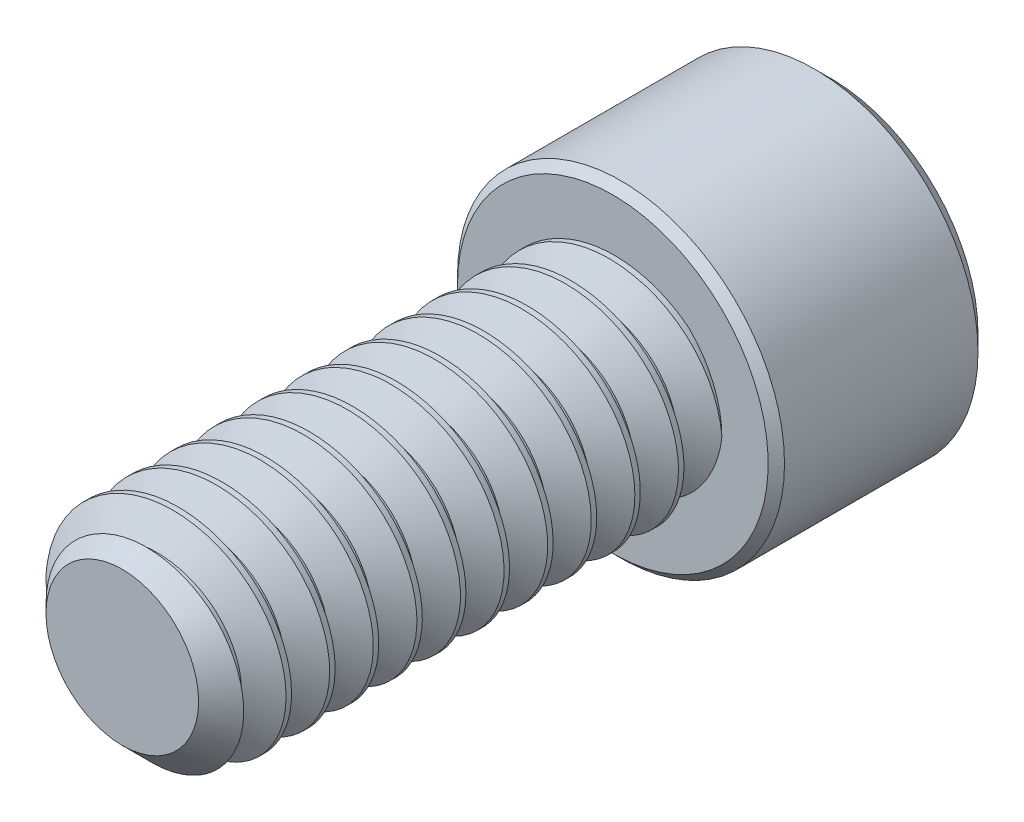
SolidWorks part; units mm, degrees
ref_plane "Front Plane" through (0, 0, 0) normal (0, 0, 1) x (1, 0, 0)
ref_plane "Top Plane" through (0, 0, 0) normal (0, 1, 0) x (1, 0, 0)
ref_plane "Right Plane" through (0, 0, 0) normal (1, 0, 0) x (0, 0, -1)
sketch "Sketch0" plane through (0, 0, 0) normal (1, 0, 0) x (0, 0, -1)
  line L0 (0, 0) -> (14.2875, 0) construction
  point P2 (20.6375, 0)
  point P4 (0, 0)
  dimension "D1" = 14.2875
  dimension "D2" = 6.35
  dimension "Min Thread" = 0
sketch "Sketch1" plane through (0, 0, 0) normal (0, 0, 1) x (1, 0, 0)
  circle A0 centre (0, 0) radius 3.175
  dimension "OD" = 6.35
extrude "Extrude1" add sketch "Sketch1" against normal blind 14.2875
sketch "Sketch2" plane through (0, 0, 0) normal (0, 0, 1) x (1, 0, 0)
  circle A0 centre (0, 0) radius 3.175 construction
  circle A1 centre (0, 0) radius 3.175
curve "Helix/Spiral1" pitch 1.27 height 15.5575 turns 12.25 parameters "pitch"=1.27
chamfer "Chamfer3" distance 0.9525 angle 45 1 edges at (3.175, 0, 0)
sketch "Sketch3" plane through (0, 0, 0) normal (1, 0, 0) x (0, 0, -1)
  line L0 (-1.1113, 3.175) -> (-0.635, 2.3501)
  line L1 (-0.635, 2.3501) -> (-0.4763, 2.3501)
  line L2 (-0.4763, 2.3501) -> (0, 3.175)
  line L3 (-1.1113, 3.175) -> (0, 3.175)
  line L4 (-0.5556, 3.175) -> (-0.5556, 2.3501) construction
  line L5 (-0.8731, 2.7626) -> (-0.2381, 2.7626) construction
  line L6 (0, 3.175) -> (0, -3.175) construction
  dimension "D1" = 0.1588
  dimension "D2" = 0.635
  dimension "D3" = 60
sweep "Cut-Sweep1" cut profiles "Sketch3" path "Helix/Spiral1"
sketch "Sketch5" plane through (0, 0, 0) normal (1, 0, 0) x (0, 0, -1)
  line L0 (14.2875, 0) -> (14.2875, 2.9183) construction
  line L1 (14.2875, 3.175) -> (0, 3.175)
  line L2 (14.2875, 3.175) -> (14.2875, 0)
  line L3 (14.2875, 0) -> (-1.1556, 0)
  line L4 (0, 0) -> (14.2875, 0) construction
  line L5 (0, 3.175) -> (-1.1556, 0)
  line L6 (0, 0) -> (16.8275, 0) construction
  dimension "D1" = 70
  dimension "D3" = 2.54
revolve "partially thread" [suppressed] add sketch "Sketch5" angle 360 about L6
sketch "Sketch6" plane through (0, 0, -14.2875) normal (0, 0, -1) x (-1, 0, 0)
  circle A0 centre (0, 0) radius 4.7625
  dimension "head dia" = 9.525
extrude "Extrude2" add sketch "Sketch6" along normal blind 6.35
sketch "Sketch7" plane through (0, 0, -20.6375) normal (0, 0, -1) x (-1, 0, 0)
  line L1 (0, 2.7496) -> (-2.3813, 1.3748)
  line L2 (-2.3813, 1.3748) -> (-2.3813, -1.3748)
  line L3 (-2.3813, -1.3748) -> (0, -2.7496)
  line L4 (0, -2.7496) -> (2.3813, -1.3748)
  line L5 (2.3813, -1.3748) -> (2.3813, 1.3748)
  line L6 (2.3813, 1.3748) -> (0, 2.7496)
  circle A0 centre (0, 0) radius 2.3813 construction
  dimension "hex dia" = 4.7625
extrude "Cut-Extrude1" cut sketch "Sketch7" against normal blind 3.5719
sketch "Sketch8" plane through (0, 0, -20.6375) normal (0, 0, -1) x (-1, 0, 0)
  circle A0 centre (0, 0) radius 2.7496
extrude "Cut-Extrude2" cut sketch "Sketch8" against normal through all draft 45
chamfer "Chamfer1" distance 0.4763 angle 45 1 edges at (-4.7625, 0, -20.6375)
chamfer "Chamfer2" distance 0.2381 angle 45 1 edges at (-4.7625, 0, -14.2875)
sketch "Sketch9" plane through (0, 0, 0) normal (1, 0, 0) x (0, 0, -1)
  line L0 (0, 3.175) -> (0, -3.175) construction
  line L1 (3.175, 3.175) -> (3.175, -3.175) construction
  line L2 (20.6375, 4.7625) -> (20.6375, -4.7625) construction
  line L3 (14.2875, 4.7625) -> (14.2875, -4.7625) construction
  line L4 (14.2875, 4.5244) -> (14.2875, -4.5244) construction
  line L5 (20.6375, -4.2863) -> (20.6375, 4.2863) construction
  line L6 (14.2875, -4.7625) -> (14.2875, 4.7625) construction
  line L7 (0, 2.2225) -> (0, -2.2225) construction
  line L8 (-1.1113, 3.175) -> (0, 3.175) construction
  line L9 (3.175, 0) -> (0, 0) construction
  dimension "D1" = 3.175
equation "\"D3@Helix/Spiral1\" = \"screw length@Extrude1\"+\"pitch@Helix/Spiral1\""
equation "\"D1@Sketch3\" = \"pitch@Helix/Spiral1\"*.125"
equation "\"D2@Sketch3\" = \"pitch@Helix/Spiral1\"*.5"
equation "\"D1@Cut-Extrude1\" = \"hex dia@Sketch7\"*.75"
equation "\"D1@Chamfer1\" = \"head dia@Sketch6\"*.05"
equation "\"D1@Sketch9\" = \"pitch@Helix/Spiral1\"*2.50"
equation "\"D1@Chamfer2\" = \"D1@Chamfer1\"/2"
equation "\"D1@Chamfer3\" = \"pitch@Helix/Spiral1\"*.750"
equation "\"D1@Sketch0\" = \"screw length@Extrude1\""
equation "\"D2@Sketch0\" = \"head depth@Extrude2\""
